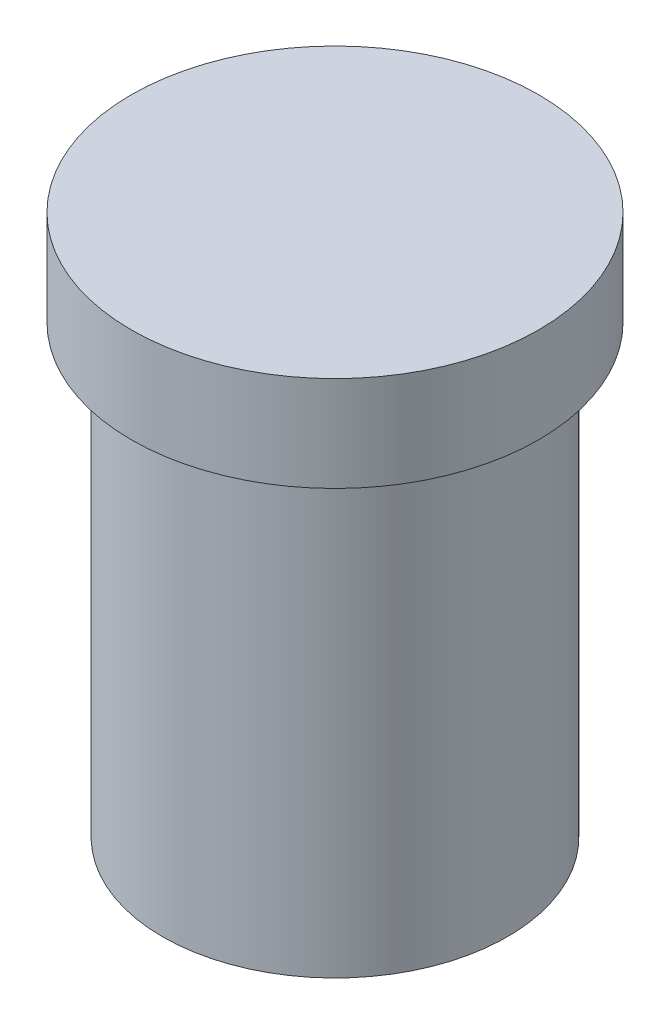
SolidWorks part; units mm, degrees
ref_plane "Front" through (0, 0, 0) normal (0, 0, 1) x (1, 0, 0)
ref_plane "Top" through (0, 0, 0) normal (0, 1, 0) x (1, 0, 0)
ref_plane "Right" through (0, 0, 0) normal (1, 0, 0) x (0, 0, -1)
sketch "Esboço1" plane through (0, 0, 0) normal (0, 1, 0) x (1, 0, 0)
  circle A0 centre (0, 0) radius 6.85
  dimension "D1" = 13.7
extrude "Ressalto-extrusão1" add sketch "Esboço1" along normal blind 3.2
sketch "Esboço3" plane through (0, 0, 0) normal (0, -1, 0) x (1, 0, 0)
  circle A0 centre (0, 0) radius 5.8
  dimension "D1" = 11.6
extrude "Ressalto-extrusão2" add sketch "Esboço3" along normal blind 15
sketch "Esboço4" plane through (0, -15, 0) normal (0, -1, 0) x (1, 0, 0)
extrude "Ressalto-extrusão3" add sketch "Esboço3<2>" along normal blind 15
sketch "Esboço3<2>" plane through (0, 0, 0) normal (0, -1, 0) x (1, 0, 0) same geometry as "Esboço3"
